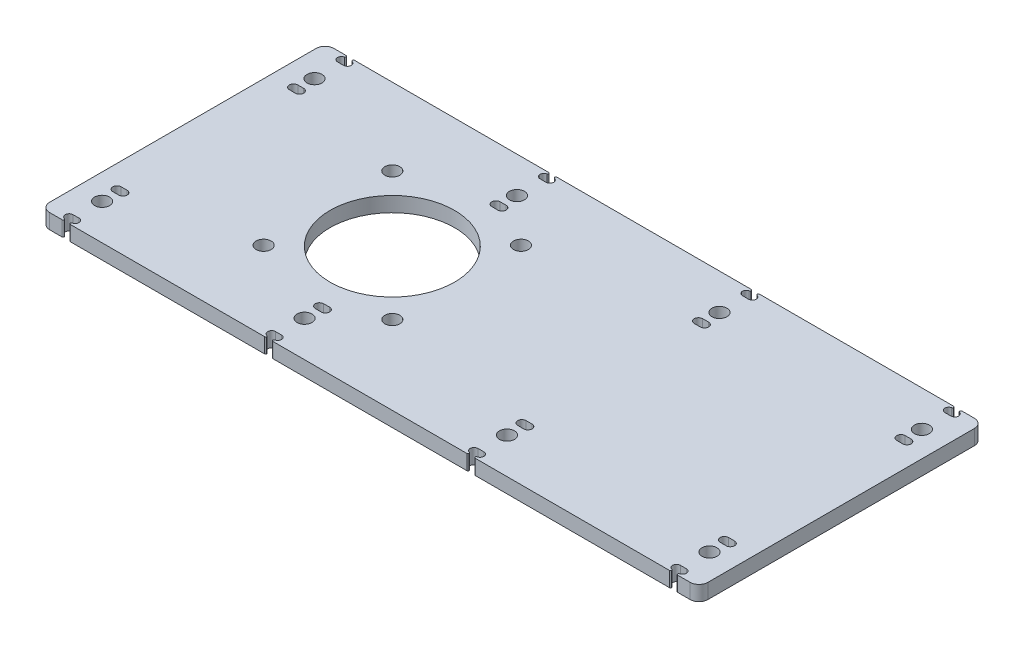
SolidWorks part; units mm, degrees
material "6061 Alloy"
ref_plane "Front Plane" through (0, 0, 0) normal (0, 0, 1) x (1, 0, 0)
ref_plane "Top Plane" through (0, 0, 0) normal (0, 1, 0) x (1, 0, 0)
ref_plane "Right Plane" through (0, 0, 0) normal (1, 0, 0) x (0, 0, -1)
sketch "Sketch1" plane through (0, 0, 0) normal (0, 1, 0) x (1, 0, 0)
  line L0 (15.0003, 37.3769) -> (15.1232, 37.3769) construction
  line L1 (0, -10) -> (190, -10)
  line L2 (0, -10) -> (0, 85) construction
  line L3 (0, 85) -> (190, 85)
  line L4 (190, -10) -> (190, 85)
  line L5 (0, 85) -> (-30, 85)
  line L6 (-30, 85) -> (-30, -10)
  line L7 (-30, -10) -> (0, -10)
  arc A0 (19.2472, 36.099) -> (19.2288, 38.5948) centre (40, 37.5) ccw
  circle A1 centre (40, 12.5) radius 2.5 construction
  circle A2 centre (40, 37.5) radius 25 construction
  circle A3 centre (64.9997, 37.3769) radius 2.5 construction
  circle A4 centre (40, 62.5) radius 2.5 construction
  circle A5 centre (40, 37.5) radius 20.8
  circle A6 centre (15.0003, 37.3769) radius 2.5 construction
  point P12 (40, 37.5)
  dimension "D1" = 41.6
  dimension "D2" = 5
  dimension "D3" = 50
  dimension "D4" = 95
  dimension "D5" = 47.5
  dimension "D6" = 190
  dimension "D7" = 30
extrude "Boss-Extrude1" add sketch "Sketch1" along normal blind 5 contours L1 L4 L3 L2 A6 A5 A0 A4 A3 A1 region at (82.7822, 0, -37.5)
extrude "Cut-Extrude1" cut sketch "Sketch2" against normal through all
sketch "Sketch2" plane through (-147.2744, 0, -165.5318) normal (0, -1, 0) x (1, 0, 0)
  circle A4 centre (208.4876, 149.245) radius 2.5
  circle A5 centre (208.4876, 106.245) radius 2.5
  circle A6 centre (165.4876, 149.245) radius 2.5
  circle A7 centre (165.4876, 106.245) radius 2.5
sketch "Sketch5" plane through (0, 0, 0) normal (0, -1, 0) x (-1, 0, 0)
  line L0 (20.5, 67) -> (22.5, 67) construction
  line L1 (20.5, 68.4) -> (22.5, 68.4)
  line L2 (20.5, 65.6) -> (22.5, 65.6)
  line L3 (20.5, 83) -> (22.5, 83) construction
  line L5 (20.5, 81.7) -> (22.5, 81.7)
  line L6 (-47.16, 67) -> (-45.16, 67) construction
  line L7 (-47.16, 68.4) -> (-45.16, 68.4)
  line L8 (-47.16, 65.6) -> (-45.16, 65.6)
  line L9 (-47.16, 83) -> (-45.16, 83) construction
  line L11 (-47.16, 81.7) -> (-45.16, 81.7)
  line L12 (-114.82, 67) -> (-112.82, 67) construction
  line L13 (-114.82, 68.4) -> (-112.82, 68.4)
  line L14 (-114.82, 65.6) -> (-112.82, 65.6)
  line L15 (-114.82, 83) -> (-112.82, 83) construction
  line L17 (-114.82, 81.7) -> (-112.82, 81.7)
  line L18 (-182.48, 67) -> (-180.48, 67) construction
  line L19 (-182.48, 68.4) -> (-180.48, 68.4)
  line L20 (-182.48, 65.6) -> (-180.48, 65.6)
  line L21 (-182.48, 83) -> (-180.48, 83) construction
  line L23 (-182.48, 81.7) -> (-180.48, 81.7)
  line L24 (30, 37.5) -> (-13.0439, 37.5) construction
  line L25 (30, 85) -> (30, -10) construction
  line L26 (-182.48, -8) -> (-180.48, -8) construction
  line L29 (-114.82, -8) -> (-112.82, -8) construction
  line L32 (-47.16, -8) -> (-45.16, -8) construction
  line L35 (20.5, -8) -> (22.5, -8) construction
  line L38 (-180.48, -10) -> (-182.48, -10)
  line L41 (-180.48, -9.3) -> (-180.48, -10)
  line L44 (-182.48, -9.3) -> (-182.48, -10)
  line L47 (-112.82, -10) -> (-114.82, -10)
  line L50 (30, 85) -> (-190, 85) construction
  line L51 (22.5, 84.3) -> (22.5, 85)
  line L52 (20.5, 84.3) -> (20.5, 85)
  line L53 (22.5, 85) -> (20.5, 85)
  line L54 (-47.16, 84.3) -> (-47.16, 85)
  line L55 (-45.16, 84.3) -> (-45.16, 85)
  line L56 (-45.16, 85) -> (-47.16, 85)
  line L57 (-114.82, 84.3) -> (-114.82, 85)
  line L58 (-112.82, 84.3) -> (-112.82, 85)
  line L59 (-112.82, 85) -> (-114.82, 85)
  line L60 (-182.48, 84.3) -> (-182.48, 85)
  line L61 (-180.48, 84.3) -> (-180.48, 85)
  line L62 (-180.48, 85) -> (-182.48, 85)
  line L63 (-112.82, -9.3) -> (-112.82, -10)
  line L64 (-114.82, -9.3) -> (-114.82, -10)
  line L65 (-45.16, -10) -> (-47.16, -10)
  line L66 (-45.16, -9.3) -> (-45.16, -10)
  line L83 (-47.16, -9.3) -> (-47.16, -10)
  line L84 (22.5, -10) -> (20.5, -10)
  line L85 (20.5, -9.3) -> (20.5, -10)
  line L86 (22.5, -9.3) -> (22.5, -10)
  line L87 (-182.48, -6.7) -> (-180.48, -6.7)
  line L88 (-114.82, -6.7) -> (-112.82, -6.7)
  line L89 (-47.16, -6.7) -> (-45.16, -6.7)
  line L90 (20.5, -6.7) -> (22.5, -6.7)
  line L91 (-182.48, 8) -> (-180.48, 8) construction
  line L92 (-182.48, 6.6) -> (-180.48, 6.6)
  line L93 (-182.48, 9.4) -> (-180.48, 9.4)
  line L94 (-114.82, 8) -> (-112.82, 8) construction
  line L95 (-114.82, 6.6) -> (-112.82, 6.6)
  line L96 (-114.82, 9.4) -> (-112.82, 9.4)
  line L97 (-47.16, 8) -> (-45.16, 8) construction
  line L98 (-47.16, 6.6) -> (-45.16, 6.6)
  line L99 (-47.16, 9.4) -> (-45.16, 9.4)
  line L100 (20.5, 8) -> (22.5, 8) construction
  line L101 (20.5, 6.6) -> (22.5, 6.6)
  line L102 (20.5, 9.4) -> (22.5, 9.4)
  circle A0 centre (21.5, 73) radius 2.5
  arc A1 (20.5, 68.4) -> (20.5, 65.6) centre (20.5, 67) ccw
  arc A2 (22.5, 65.6) -> (22.5, 68.4) centre (22.5, 67) ccw
  arc A3 (20.5, 84.3) -> (20.5, 81.7) centre (20.5, 83) ccw
  arc A4 (22.5, 81.7) -> (22.5, 84.3) centre (22.5, 83) ccw
  circle A5 centre (-46.16, 73) radius 2.5
  arc A6 (-47.16, 68.4) -> (-47.16, 65.6) centre (-47.16, 67) ccw
  arc A7 (-45.16, 65.6) -> (-45.16, 68.4) centre (-45.16, 67) ccw
  arc A8 (-47.16, 84.3) -> (-47.16, 81.7) centre (-47.16, 83) ccw
  arc A9 (-45.16, 81.7) -> (-45.16, 84.3) centre (-45.16, 83) ccw
  circle A10 centre (-113.82, 73) radius 2.5
  arc A11 (-114.82, 68.4) -> (-114.82, 65.6) centre (-114.82, 67) ccw
  arc A12 (-112.82, 65.6) -> (-112.82, 68.4) centre (-112.82, 67) ccw
  arc A13 (-114.82, 84.3) -> (-114.82, 81.7) centre (-114.82, 83) ccw
  arc A14 (-112.82, 81.7) -> (-112.82, 84.3) centre (-112.82, 83) ccw
  circle A15 centre (-181.48, 73) radius 2.5
  arc A16 (-182.48, 68.4) -> (-182.48, 65.6) centre (-182.48, 67) ccw
  arc A17 (-180.48, 65.6) -> (-180.48, 68.4) centre (-180.48, 67) ccw
  arc A18 (-182.48, 84.3) -> (-182.48, 81.7) centre (-182.48, 83) ccw
  arc A19 (-180.48, 81.7) -> (-180.48, 84.3) centre (-180.48, 83) ccw
  arc A48 (-180.48, -6.7) -> (-180.48, -9.3) centre (-180.48, -8) cw
  arc A49 (-182.48, -9.3) -> (-182.48, -6.7) centre (-182.48, -8) cw
  circle A50 centre (-181.48, 2) radius 2.5
  arc A51 (-112.82, -6.7) -> (-112.82, -9.3) centre (-112.82, -8) cw
  arc A52 (-114.82, -9.3) -> (-114.82, -6.7) centre (-114.82, -8) cw
  circle A53 centre (-113.82, 2) radius 2.5
  arc A54 (-45.16, -6.7) -> (-45.16, -9.3) centre (-45.16, -8) cw
  arc A55 (-47.16, -9.3) -> (-47.16, -6.7) centre (-47.16, -8) cw
  circle A56 centre (-46.16, 2) radius 2.5
  arc A57 (22.5, -6.7) -> (22.5, -9.3) centre (22.5, -8) cw
  arc A58 (20.5, -9.3) -> (20.5, -6.7) centre (20.5, -8) cw
  circle A59 centre (21.5, 2) radius 2.5
  arc A60 (-182.48, 6.6) -> (-182.48, 9.4) centre (-182.48, 8) cw
  arc A61 (-180.48, 9.4) -> (-180.48, 6.6) centre (-180.48, 8) cw
  arc A62 (-114.82, 6.6) -> (-114.82, 9.4) centre (-114.82, 8) cw
  arc A63 (-112.82, 9.4) -> (-112.82, 6.6) centre (-112.82, 8) cw
  arc A64 (-47.16, 6.6) -> (-47.16, 9.4) centre (-47.16, 8) cw
  arc A65 (-45.16, 9.4) -> (-45.16, 6.6) centre (-45.16, 8) cw
  arc A66 (20.5, 6.6) -> (20.5, 9.4) centre (20.5, 8) cw
  arc A67 (22.5, 9.4) -> (22.5, 6.6) centre (22.5, 8) cw
  point P7 (21.5, 67)
  point P16 (21.5, 83)
  point P26 (-46.16, 67)
  point P33 (-46.16, 83)
  point P42 (-113.82, 67)
  point P49 (-113.82, 83)
  point P58 (-181.48, 67)
  point P65 (-181.48, 83)
  point P112 (-181.48, -8)
  point P115 (-181.48, 8)
  point P120 (-113.82, -8)
  point P123 (-113.82, 8)
  point P128 (-46.16, -8)
  point P131 (-46.16, 8)
  point P136 (21.5, -8)
  point P139 (21.5, 8)
  dimension "D1" = 1.4
  dimension "D2" = 5
  dimension "D3" = 1.3
  dimension "D10" = 2
  dimension "D5" = 8.5
  dimension "D6" = 10
  dimension "D7" = 6
  dimension "D8" = 2
  dimension "D9" = 2
  dimension "D4" = 4
  dimension "D11" = 4
extrude "Cut-Extrude5" cut sketch "Sketch5" against normal through all
fillet "Fillet1" radius 0.4 32 edges at (-20.5, 2.5, -85) (-20.5, 2.5, -84.3) (-22.5, 2.5, -85) (-22.5, 2.5, -84.3) (45.16, 2.5, -85) (45.16, 2.5, -84.3) (47.16, 2.5, -84.3) (47.16, 2.5, -85) (114.82, 2.5, -84.3) (114.82, 2.5, -85) (112.82, 2.5, -85) (112.82, 2.5, -84.3) (180.48, 2.5, -84.3) (180.48, 2.5, -85) (182.48, 2.5, -84.3) (182.48, 2.5, -85) (182.48, 2.5, 10) (182.48, 2.5, 9.3) (180.48, 2.5, 10) (180.48, 2.5, 9.3) (112.82, 2.5, 10) (112.82, 2.5, 9.3) (114.82, 2.5, 10) (114.82, 2.5, 9.3) (47.16, 2.5, 10) (45.16, 2.5, 10) (45.16, 2.5, 9.3) (47.16, 2.5, 9.3) (-22.5, 2.5, 10) (-22.5, 2.5, 9.3) (-20.5, 2.5, 10) (-20.5, 2.5, 9.3)
fillet "Fillet2" radius 3 4 edges at (-30, 2.5, -85) (190, 2.5, -85) (190, 2.5, 10) (-30, 2.5, 10)
